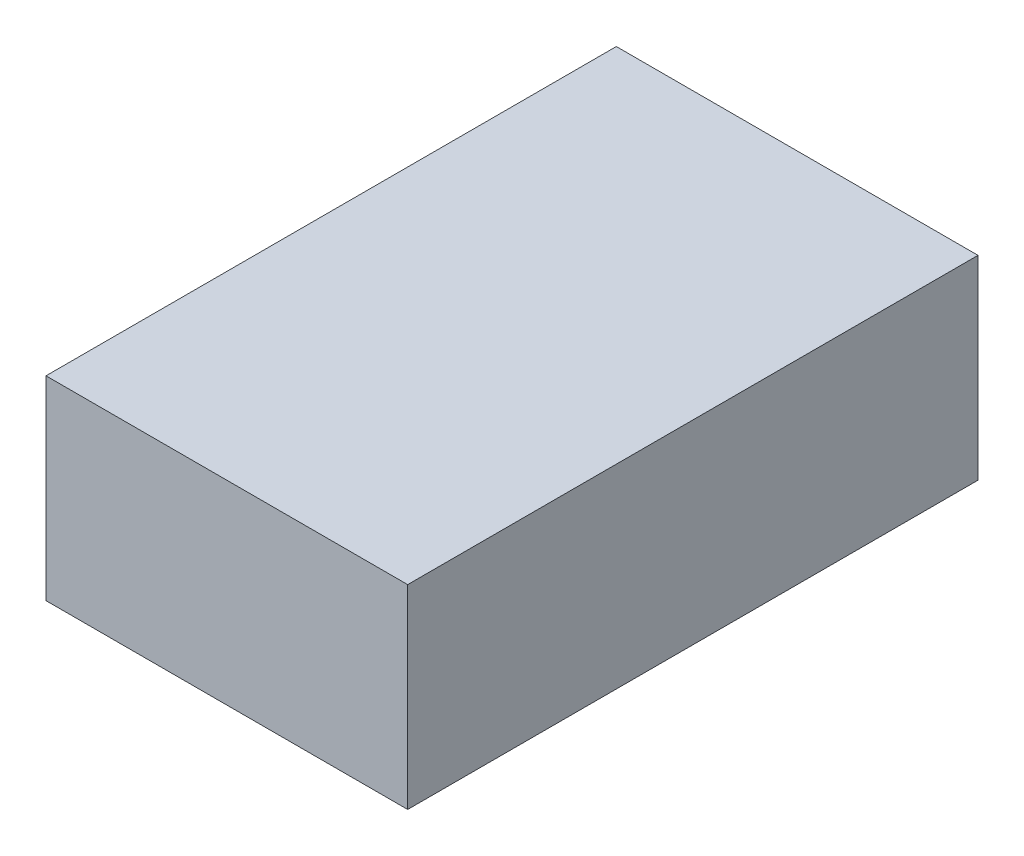
SolidWorks part; units mm, degrees
ref_plane "Front Plane" through (0, 0, 0) normal (0, 0, 1) x (1, 0, 0)
ref_plane "Top Plane" through (0, 0, 0) normal (0, 1, 0) x (1, 0, 0)
ref_plane "Right Plane" through (0, 0, 0) normal (1, 0, 0) x (0, 0, -1)
sketch "Sketch1" plane through (0, 0, 0) normal (0, 1, 0) x (1, 0, 0)
  line L1 (-33.02, -52.07) -> (33.02, -52.07)
  line L2 (-33.02, -52.07) -> (-33.02, 52.07)
  line L3 (-33.02, 52.07) -> (33.02, 52.07)
  line L4 (33.02, -52.07) -> (33.02, 52.07)
  line L5 (-33.02, -52.07) -> (33.02, 52.07) construction
  line L6 (-33.02, 52.07) -> (33.02, -52.07) construction
  point P0 (0, 0)
  dimension "D1" = 66.04
  dimension "D2" = 104.14
extrude "Boss-Extrude1" add sketch "Sketch1" along normal blind 35.56
